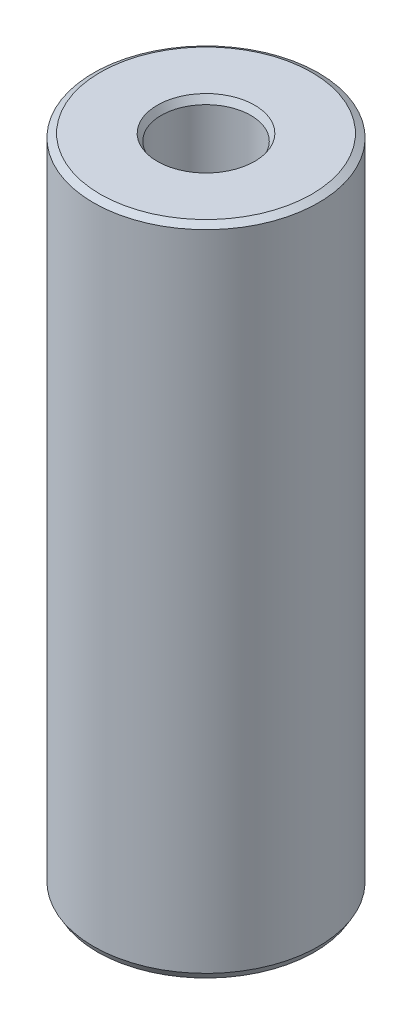
SolidWorks part; units mm, degrees
ref_plane "Front Plane" through (0, 0, 0) normal (0, 0, 1) x (1, 0, 0)
ref_plane "Top Plane" through (0, 0, 0) normal (0, 1, 0) x (1, 0, 0)
ref_plane "Right Plane" through (0, 0, 0) normal (1, 0, 0) x (0, 0, -1)
sketch "Sketch1" plane through (0, 0, 0) normal (0, 1, 0) x (1, 0, 0)
  circle A0 centre (0, 0) radius 47.5
  dimension "SLEEVE_OD" = 95
extrude "Boss-Extrude1" add sketch "Sketch1" along normal blind 276.476
sketch "Sketch2" plane through (0, 0, 0) normal (0, 1, 0) x (1, 0, 0)
  circle A0 centre (0, 0) radius 18.8998
  dimension "BORE_D" = 37.7996
extrude "Cut-Extrude1" cut sketch "Sketch2" along normal through all
chamfer "Chamfer1" distance 1.6626 angle 60 4 edges at (0, 276.476, 18.8998) (0, 0, 18.8998) (0, 0, 47.5) (0, 276.476, 47.5) first distance on face at (0, 276.476, 18.8998) first distance on face at (0, 0, 18.8998) first distance on face at (0, 276.476, 47.5)
